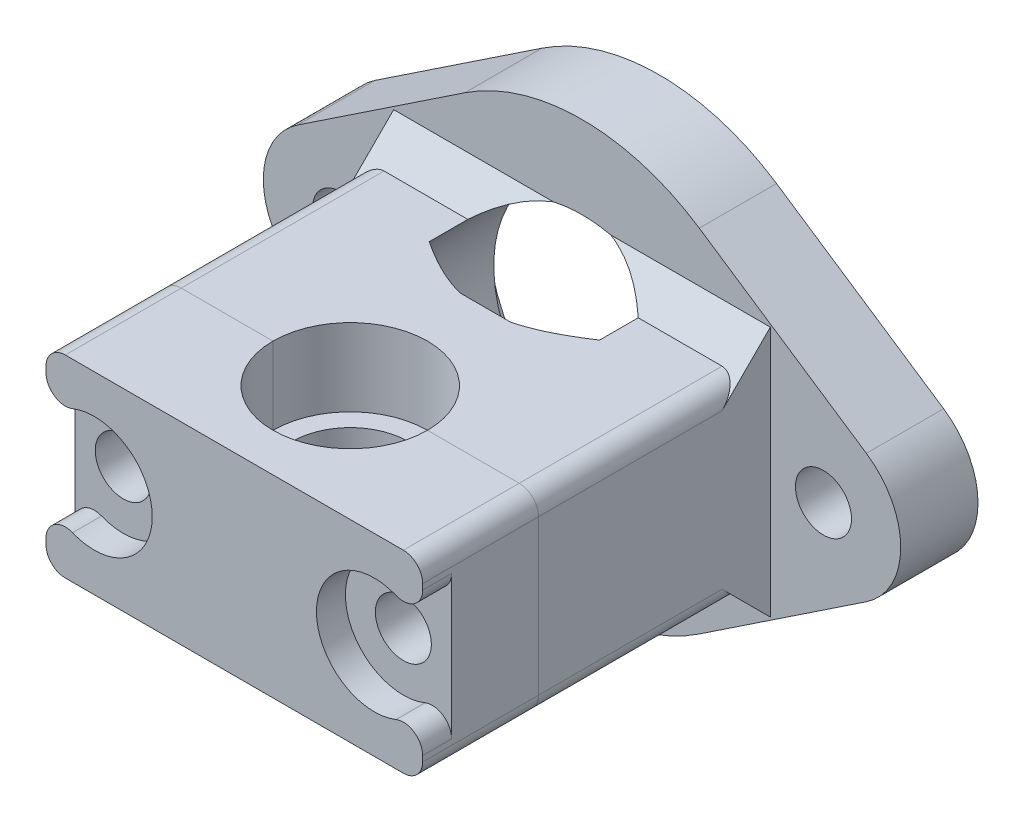
SolidWorks part; units mm, degrees
note: The reader was unsure of these and kept them because the rebuilt part matched: shared geometry of "Sketch1<4>", "Sketch1<6>", "Sketch9<3>", "Sketch9<4>".
material "ABS"
ref_plane "Front Plane" through (0, 0, 0) normal (0, 0, 1) x (1, 0, 0)
ref_plane "Top Plane" through (0, 0, 0) normal (0, 1, 0) x (1, 0, 0)
ref_plane "Right Plane" through (0, 0, 0) normal (1, 0, 0) x (0, 0, -1)
other "Configuration Table"
sketch "Sketch1" plane through (0, 0, 0) normal (0, 0, 1) x (1, 0, 0)
  line L0 (-12.5, 0) -> (12.5, 0)
  line L1 (-6.0703, -9.0984) -> (-14.72, -3.3274)
  line L2 (-6.0703, 9.0984) -> (-14.72, 3.3274)
  line L3 (6.0703, 9.0984) -> (14.72, 3.3274)
  line L4 (6.0703, -9.0984) -> (14.72, -3.3274)
  circle A0 centre (0, 0) radius 6.6675
  circle A1 centre (0, 0) radius 8.9375
  circle A2 centre (0, 0) radius 10.9375
  circle A3 centre (-12.5, 0) radius 4
  circle A4 centre (12.5, 0) radius 4
  point P7 (0, 0)
  dimension "D1" = 13.335
  dimension "D2" = 17.875
  dimension "D4" = 8
  dimension "D3" = 2
  dimension "D5" = 25
extrude "Boss-Extrude1" add sketch "Sketch1" along normal blind 4
extrude "Cut-Extrude1" cut sketch "Sketch1<4>" against normal through all both and the other way through all contours L0 A0 | L0 A0
sketch "Sketch1<4>" plane through (0, 0, 0) normal (0, 0, 1) x (1, 0, 0) same geometry as "Sketch1"
extrude "Cut-Extrude2" cut sketch "Sketch1<6>" along normal blind 1.9 and the other way through all contours A1
sketch "Sketch1<6>" plane through (0, 0, 0) normal (0, 0, 1) x (1, 0, 0) same geometry as "Sketch1"
hole_wizard "M2.5 Clearance Hole1" positions "Sketch2" profile "Sketch3" hole size "M2.5" standard "ANSI Metric" end condition through all
sketch "Sketch2" plane through (0, 0, 4) normal (0, 0, 1) x (1, 0, 0)
  point P0 (-12.5, 0)
  point P3 (12.5, 0)
sketch "Sketch3" plane through (-12.5, 0, 4) normal (1, 0, 0) x (0, -1, 0)
  line L0 (0, 0) -> (0, 4)
  line L1 (0, 4) -> (1.45, 4)
  line L2 (1.45, 4) -> (1.45, 0)
  line L5 (1.45, 0) -> (0, 0)
  line L11 (0, -6.35) -> (0, 107.95) construction
  dimension "Thru Hole Dia." = 2.9
  dimension "Thru Hole Depth" = 4
chamfer "Chamfer1" [suppressed] distance 0.25 angle 45
sketch "Sketch4" plane through (0, 0, 4) normal (0, 0, 1) x (1, 0, 0)
  line L1 (-9.75, 5) -> (9.75, 5)
  line L3 (-9.75, -5) -> (9.75, -5)
  line L4 (9.75, 5) -> (9.75, -5)
  line L5 (-9.75, -5) -> (-9.75, 5)
  line L17 (0, 5) -> (0, -5) construction
  circle A0 centre (-12.5, 0) radius 1.45 construction
  point P0 (2.6369, -5)
  point P1 (0, -5)
  point P15 (0, 0)
  dimension "D1" = 2.75
  dimension "D2" = 10
extrude "Boss-Extrude2" add sketch "Sketch4" along normal blind 12 contours L1 L4 L3 L5
sketch "Sketch6" plane through (0, 0, 4) normal (0, 0, -1) x (-1, 0, 0)
  circle A0 centre (0, 0) radius 6.6675 construction
  circle A1 centre (0, 0) radius 6.6675
extrude "Cut-Extrude3" cut sketch "Sketch6" against normal blind 5
sketch "Sketch8" plane through (0, 0, 16) normal (0, 0, 1) x (1, 0, 0)
  line L4 (-9.75, 5) -> (-9.75, -5)
  line L5 (-9.75, -5) -> (9.75, -5)
  line L6 (9.75, -5) -> (9.75, 5)
  line L10 (9.75, 5) -> (-9.75, 5)
  line L11 (-9.75, 5) -> (-9.75, -5)
  line L18 (-9.75, -5) -> (9.75, -5)
  line L19 (9.75, -5) -> (9.75, 5)
  line L20 (9.75, 5) -> (-9.75, 5)
  dimension "D1" = 0
extrude "Boss-Extrude3" add sketch "Sketch8" along normal blind 6 separate body
sketch "Sketch9" plane through (0, 0, 0) normal (0, 1, 0) x (1, 0, 0)
  line L1 (-4, -16) -> (4, -16)
  line L2 (-9.75, -16) -> (9.75, -16) construction
  circle A0 centre (0, -16) radius 4
  circle A1 centre (0, -16) radius 3
  point P2 (0, -16)
  dimension "D1" = 8
  dimension "D2" = 1
extrude "Cut-Extrude4" cut sketch "Sketch9" against normal through all both and the other way through all contours A0
extrude "Boss-Extrude4" add sketch "Sketch9<3>" along normal mid plane 2 contours A0 A1
sketch "Sketch9<3>" plane through (0, 0, 0) normal (0, 1, 0) x (1, 0, 0) same geometry as "Sketch9"
extrude "Boss-Extrude5" add sketch "Sketch9<4>" along normal mid plane 2 contours A1 L1 A0
sketch "Sketch9<4>" plane through (0, 0, 0) normal (0, 1, 0) x (1, 0, 0) same geometry as "Sketch9"
sketch "Sketch10" plane through (0, 0, 22) normal (0, 0, 1) x (1, 0, 0)
  line L0 (-7.25, 0) -> (7.25, 0) construction
  line L1 (9.75, 5) -> (9.75, -5) construction
  point P4 (0, 0)
  dimension "D1" = 2.5
chamfer "Chamfer2" distance 1.5 angle 45 6 edges at (-6.6675, 0, 9) (6.6675, 0, 9) (-7.0804, 5, 4) (7.0804, 5, 4) (-7.0804, -5, 4) (7.0804, -5, 4)
hole_wizard "Tap Drill for M2.5x0.45 Tap1" positions "Sketch11" profile "Sketch12" hole size "M2.5x0.45" standard "ANSI Metric"
sketch "Sketch11" plane through (0, 0, 22) normal (0, 0, 1) x (1, 0, 0)
  point P0 (-7.25, 0)
  point P3 (7.25, 0)
sketch "Sketch12" plane through (-7.25, 0, 22) normal (1, 0, 0) x (0, -1, 0)
  line L0 (0, 0) -> (0, 13.6159)
  line L1 (0, 13.6159) -> (1.025, 13)
  line L2 (1.025, 13) -> (1.025, 0)
  line L5 (1.025, 0) -> (0, 0)
  line L10 (0, 13.6159) -> (-1.025, 13) construction
  line L11 (0, -6.35) -> (0, 107.95) construction
  dimension "Hole Dia." = 2.05
  dimension "Hole Depth" = 13
  dimension "Drill Angle" = 118
hole_wizard "CBORE for M2.5 Pan Head Machine Screw1" positions "Sketch13" profile "Sketch14" counterbore size "M2.5" standard "ANSI Metric" end condition through all
sketch "Sketch13" plane through (0, 0, 22) normal (0, 0, 1) x (1, 0, 0)
  point P0 (7.25, 0)
  point P3 (-7.25, 0)
sketch "Sketch14" plane through (7.25, 0, 22) normal (1, 0, 0) x (0, -1, 0)
  line L0 (0, 0) -> (0, 22)
  line L1 (0, 22) -> (1.45, 22)
  line L3 (1.45, 22) -> (1.45, 1.5)
  line L4 (1.45, 1.5) -> (3, 1.5)
  line L5 (3, 1.5) -> (3, 0)
  line L7 (3, 0) -> (0, 0)
  line L11 (0, -6.35) -> (0, 107.95) construction
  dimension "Thru Hole Dia." = 2.9
  dimension "Thru Hole Depth" = 22
  dimension "C'Bore Dia." = 6
  dimension "C'Bore Depth" = 1.5
fillet "Fillet1" radius 1 4 edges at (9.75, 5, 10.75) (9.75, -5, 10.75) (-9.75, -5, 10.75) (-9.75, 5, 10.75)
fillet "Fillet2" radius 1 8 edges at (9.75, 5, 19) (-9.75, 5, 19) (-9.75, -5, 19) (9.75, -5, 19) (-9.75, 1.6583, 21.25) (-9.75, -1.6583, 21.25) (9.75, -1.6583, 21.25) (9.75, 1.6583, 21.25)
other "Save Bodies1"
equation "\"D2@Sketch1\"=15.875mm+2"
